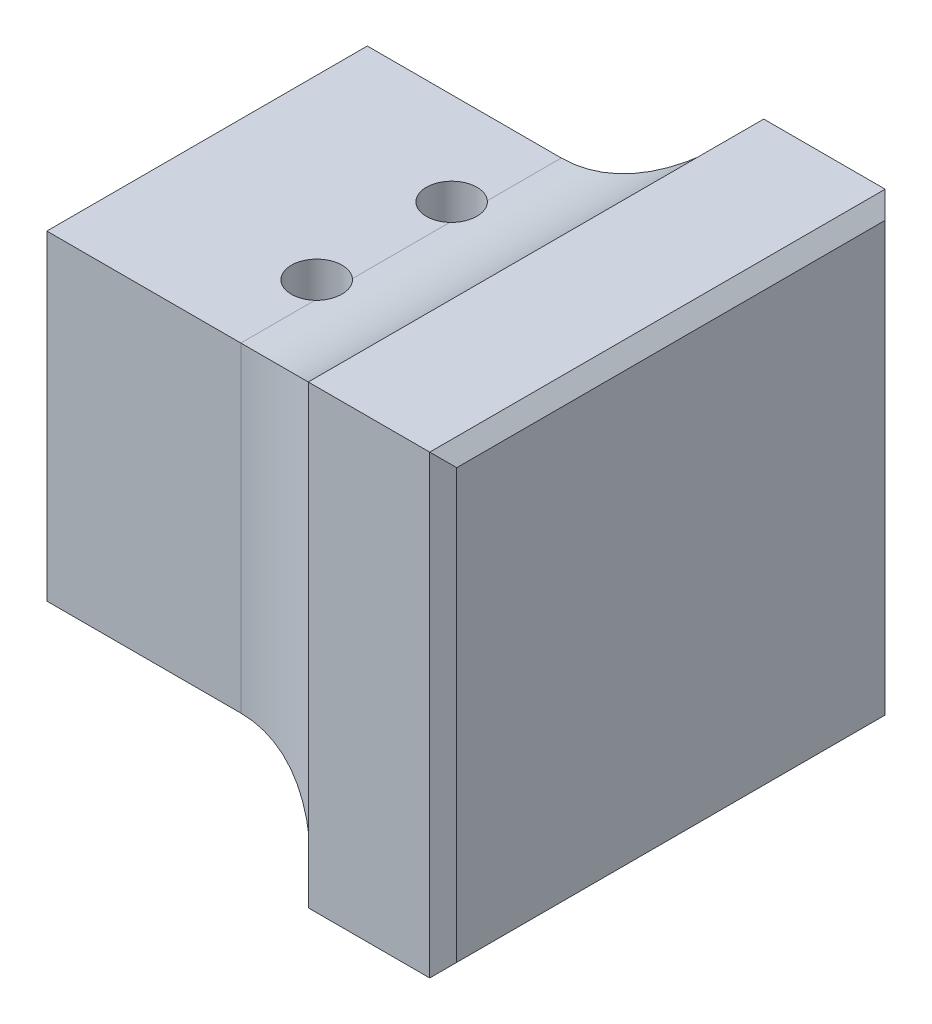
SolidWorks part; units mm, degrees
ref_plane "Front Plane" through (0, 0, 0) normal (0, 0, 1) x (1, 0, 0)
ref_plane "Top Plane" through (0, 0, 0) normal (0, 1, 0) x (1, 0, 0)
ref_plane "Right Plane" through (0, 0, 0) normal (1, 0, 0) x (0, 0, -1)
sketch "Sketch1" plane through (0, 0, 0) normal (0, 1, 0) x (1, 0, 0)
  line L1 (0, 0) -> (21, 0)
  line L2 (0, 0) -> (0, 19)
  line L3 (0, 19) -> (21, 19)
  line L4 (21, 0) -> (21, 19)
  circle A0 centre (12, 13.5) radius 1.5
  circle A1 centre (12, 5.5) radius 1.5
  point P9 (0, 0)
  dimension "D3" = 3
  dimension "D1" = 19
  dimension "D2" = 21
  dimension "D4" = 9
  dimension "D5" = 5.5
  dimension "D6" = 5.5
extrude "Boss-Extrude1" add sketch "Sketch1" along normal blind 19
chamfer "Chamfer1" distance 1.5 angle 45 4 edges at (0, 9.5, -19) (0, 19, -9.5) (0, 9.5, 0) (0, 0, -9.5)
sketch "Sketch2" plane through (21, 0, 0) normal (1, 0, 0) x (0, 0, -1)
  line L0 (19, 19) -> (19, 0) construction
  line L1 (-4, -4) -> (23, -4)
  line L2 (-4, -4) -> (-4, 23)
  line L3 (-4, 23) -> (23, 23)
  line L4 (23, -4) -> (23, 23)
  line L5 (0, 19) -> (0, 0) construction
  line L6 (0, 19) -> (19, 19) construction
  dimension "D1" = 4
  dimension "D2" = 4
  dimension "D3" = 27
  dimension "D4" = 4
extrude "Boss-Extrude2" add sketch "Sketch2" along normal blind 8
fillet "Fillet1" radius 10 4 edges at (21, 0, -9.5) (21, 9.5, 0) (21, 19, -9.5) (21, 9.5, -19)
chamfer "Chamfer2" distance 0.8 angle 45 4 edges at (29, 23, -9.5) (29, 9.5, -23) (29, -4, -9.5) (29, 9.5, 4)
equation "\"1.5.00mm\"=1"
